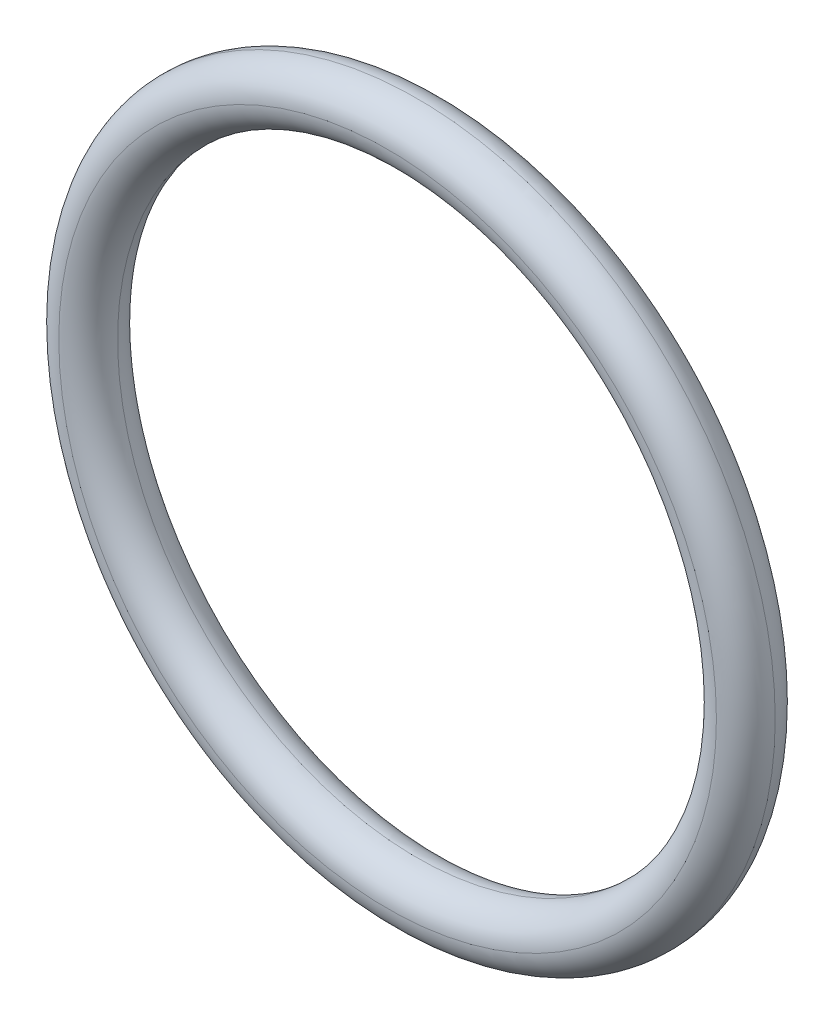
SolidWorks part; units mm, degrees
material "Caoutchouc silicone"
ref_plane "Plan de face" through (0, 0, 0) normal (0, 0, 1) x (1, 0, 0)
ref_plane "Plan de dessus" through (0, 0, 0) normal (0, 1, 0) x (1, 0, 0)
ref_plane "Plan de droite" through (0, 0, 0) normal (1, 0, 0) x (0, 0, -1)
sketch "Esquisse1" plane through (0, 0, 0) normal (0, 0, 1) x (1, 0, 0)
  circle A0 centre (0, 0) radius 37.1475
  dimension "D1" = 74.295
extrude "Boss.-Extru.1" add sketch "Esquisse1" along normal blind 6.096
sketch "Esquisse2" plane through (0, 0, 6.096) normal (0, 0, 1) x (1, 0, 0)
  circle A0 centre (0, 0) radius 31.0515
  circle A1 centre (0, 0) radius 37.1475 construction
  dimension "D1" = 6.096
extrude "Enlèv. mat.-Extru.1" cut sketch "Esquisse2" against normal through all
fillet "Congé6" radius 3.048 4 edges at (31.0515, 0, 0) (31.0515, 0, 6.096) (37.1475, 0, 0) (37.1475, 0, 6.096)
ref_plane "Plan1" through (0, 0, 3.048) normal (0, 0, 1) x (1, 0, 0)
